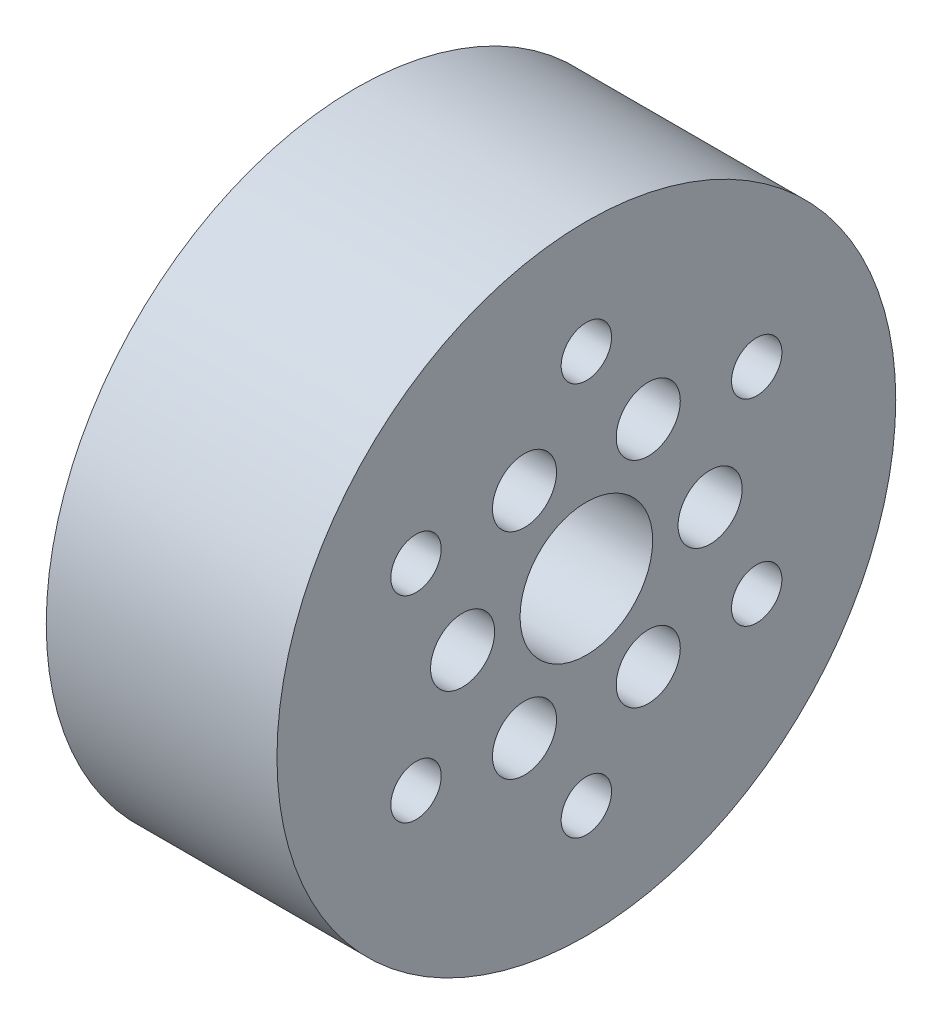
SolidWorks part; units mm, degrees
material "PLA"
ref_plane "Front Plane" through (0, 0, 0) normal (0, 0, 1) x (1, 0, 0)
ref_plane "Top Plane" through (0, 0, 0) normal (0, 1, 0) x (1, 0, 0)
ref_plane "Right Plane" through (0, 0, 0) normal (1, 0, 0) x (0, 0, -1)
sketch "Sketch13" plane through (0, 0, 0) normal (1, 0, 0) x (0, 0, -1)
  circle A0 centre (0, 0) radius 35
  circle A1 centre (0, 0) radius 7.5
  dimension "D1" = 70
  dimension "D2" = 15
extrude "Boss-Extrude1" add sketch "Sketch13" along normal blind 23
sketch "Sketch14" plane through (23, 0, 0) normal (1, 0, 0) x (0, 0, -1)
  line L0 (0, 0) -> (14, 0) construction
  line L1 (0, 0) -> (19.2691, -11.125) construction
  circle A0 centre (0, 0) radius 7.5 construction
  circle A1 centre (14, 0) radius 2.05
  circle A2 centre (19.2691, -11.125) radius 2.05
  circle A3 centre (7, 12.1244) radius 2.05
  circle A4 centre (19.2691, 11.125) radius 2.05
  circle A5 centre (-7, 12.1244) radius 2.05
  circle A6 centre (0, 22.25) radius 2.05
  circle A7 centre (-14, 0) radius 2.05
  circle A8 centre (-19.2691, 11.125) radius 2.05
  circle A9 centre (-7, -12.1244) radius 2.05
  circle A10 centre (-19.2691, -11.125) radius 2.05
  circle A11 centre (7, -12.1244) radius 2.05
  circle A12 centre (0, -22.25) radius 2.05
  dimension "D4" = 4.1
  dimension "D5" = 4.1
  dimension "D1" = 30
  dimension "D2" = 14
  dimension "D3" = 22.25
  dimension "D6" = 6
extrude "Cut-Extrude1" cut sketch "Sketch14" against normal through all
sketch "Sketch16" plane through (23, 0, 0) normal (1, 0, 0) x (0, 0, -1)
  circle A0 centre (-14, 0) radius 2.85
  circle A1 centre (-19.2691, -11.125) radius 2.85
  circle A2 centre (-7, -12.1244) radius 2.85
  circle A3 centre (0, -22.25) radius 2.85
  circle A4 centre (7, -12.1244) radius 2.85
  circle A5 centre (19.2691, -11.125) radius 2.85
  circle A6 centre (14, 0) radius 2.85
  circle A7 centre (19.2691, 11.125) radius 2.85
  circle A8 centre (7, 12.1244) radius 2.85
  circle A9 centre (0, 22.25) radius 2.85
  circle A10 centre (-7, 12.1244) radius 2.85
  circle A11 centre (-19.2691, 11.125) radius 2.85
  circle A12 centre (0, 0) radius 7.5 construction
  point P28 (0, 0)
  circle M1 centre (14, 0) radius 2.05
  circle M2 centre (19.2691, 11.125) radius 2.05
  circle M3 centre (7, 12.1244) radius 2.05
  circle M4 centre (0, 22.25) radius 2.05
  circle M6 centre (-19.2691, 11.125) radius 2.05
  circle M7 centre (-14, 0) radius 2.05
  circle M8 centre (-19.2691, -11.125) radius 2.05
  circle M9 centre (-7, -12.1244) radius 2.05
  circle M10 centre (0, -22.25) radius 2.05
  circle M11 centre (7, -12.1244) radius 2.05
  circle M12 centre (19.2691, -11.125) radius 2.05
  dimension "D1" = 5.7
  dimension "D2" = 5.7
  dimension "D3" = 6
extrude "Cut-Extrude2" cut sketch "Sketch16" against normal blind 16.5 contours A0 M7 | M7 | M9 | A2 M9 | A4 M11 | M11 | M1 | A8 M3 | M3 | A10 | A6 region at (23, 0, 16.7694) region at (23, -12.1244, 9.7694) region at (23, -12.1244, -4.2306) region at (23, 12.1244, -4.2306) region at (23, 0, -14) region at (23, 12.1244, -7) region at (23, 0, 14) region at (23, -12.1244, 7) region at (23, -12.1244, -7)
extrude "Cut-Extrude3" cut sketch "Sketch16<4>" against normal blind 8.5 contours A1 M8 | A11 M6 | M6 | M8 | A9 M4 | M4 | M2 | M12 | A5 M12 | M10 | A7 | A3 region at (23, -11.125, 22.0385) region at (23, -11.125, -16.4997) region at (23, 22.25, 2.7694) region at (23, 11.125, 22.0385) region at (23, 11.125, -19.2691) region at (23, 22.25, 0) region at (23, 11.125, 19.2691) region at (23, -11.125, 19.2691) region at (23, -22.25, 0) region at (23, -11.125, -19.2691)
sketch "Sketch16<4>" plane through (23, 0, 0) normal (1, 0, 0) x (0, 0, -1) same geometry as "Sketch16"
sketch "Sketch18" plane through (0, 0, 0) normal (-1, 0, 0) x (0, 0, 1)
  circle A1 centre (0, 0) radius 35
  circle A2 centre (0, 0) radius 35
  circle A3 centre (0, 0) radius 7.5
  circle A4 centre (0, 0) radius 7.5
  circle A5 centre (-14, 0) radius 2.05
  circle A6 centre (-14, 0) radius 2.05
  circle A7 centre (-19.2691, 11.125) radius 2.05
  circle A8 centre (-19.2691, 11.125) radius 2.05
  circle A9 centre (-7, 12.1244) radius 2.05
  circle A10 centre (-7, 12.1244) radius 2.05
  circle A11 centre (0, 22.25) radius 2.05
  circle A12 centre (0, 22.25) radius 2.05
  circle A13 centre (7, 12.1244) radius 2.05
  circle A14 centre (7, 12.1244) radius 2.05
  circle A15 centre (19.2691, 11.125) radius 2.05
  circle A16 centre (19.2691, 11.125) radius 2.05
  circle A17 centre (14, 0) radius 2.05
  circle A18 centre (14, 0) radius 2.05
  circle A19 centre (19.2691, -11.125) radius 2.05
  circle A20 centre (19.2691, -11.125) radius 2.05
  circle A21 centre (7, -12.1244) radius 2.05
  circle A22 centre (7, -12.1244) radius 2.05
  circle A23 centre (0, -22.25) radius 2.05
  circle A24 centre (0, -22.25) radius 2.05
  circle A25 centre (-7, -12.1244) radius 2.05
  circle A26 centre (-7, -12.1244) radius 2.05
  circle A27 centre (-19.2691, -11.125) radius 2.05
  circle A28 centre (-19.2691, -11.125) radius 2.05
  dimension "D1" = 0
  dimension "D2" = 0
  dimension "D3" = 0
  dimension "D4" = 0
  dimension "D5" = 0
  dimension "D6" = 0
  dimension "D7" = 0
  dimension "D8" = 0
  dimension "D9" = 0
  dimension "D10" = 0
  dimension "D11" = 0
  dimension "D12" = 0
  dimension "D13" = 0
  dimension "D14" = 0
extrude "Boss-Extrude2" add sketch "Sketch18" along normal blind 3.1
sketch "Sketch19" plane through (23, 0, 0) normal (1, 0, 0) x (0, 0, -1)
  circle A0 centre (-7, 12.1244) radius 3.625
  circle A1 centre (7, 12.1244) radius 3.625
  circle A2 centre (14, 0) radius 3.625
  circle A3 centre (7, -12.1244) radius 3.625
  circle A4 centre (-7, -12.1244) radius 3.625
  circle A5 centre (-14, 0) radius 3.625
  point P15 (0, 0)
  dimension "D1" = 7.25
  dimension "D2" = 6
extrude "Cut-Extrude4" cut sketch "Sketch19" against normal blind 9.5
